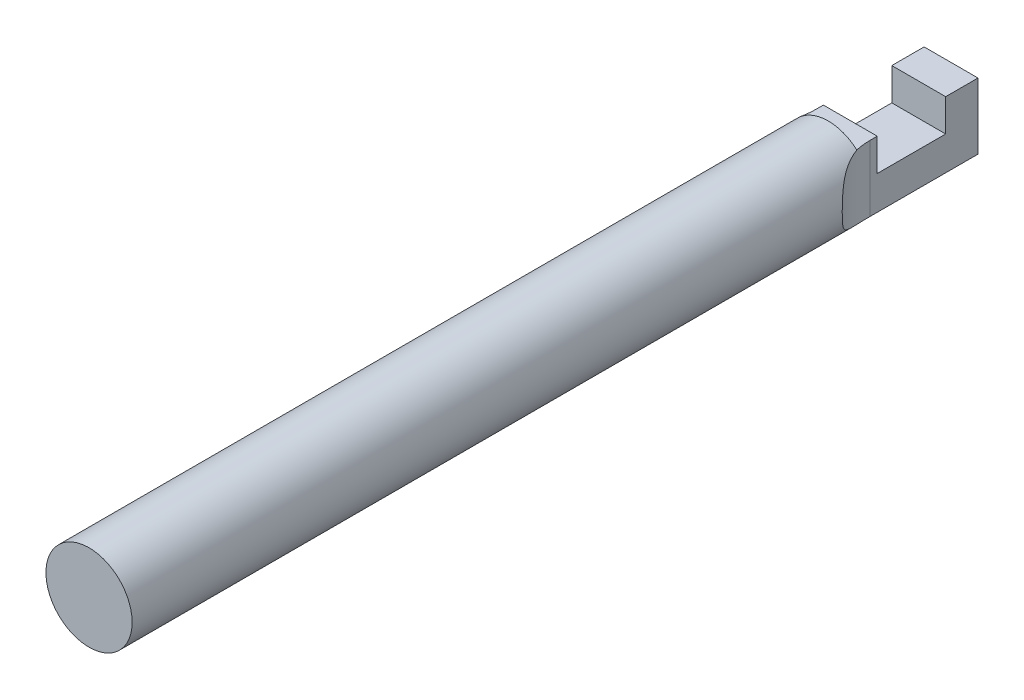
SolidWorks part; units mm, degrees
material "Alloy Steel"
ref_plane "Front" through (0, 0, 0) normal (0, 0, 1) x (1, 0, 0)
ref_plane "Top" through (0, 0, 0) normal (0, 1, 0) x (1, 0, 0)
ref_plane "Right" through (0, 0, 0) normal (1, 0, 0) x (0, 0, -1)
ref_axis "X" through (-80.9, 0, 0) along (1, 0, 0)
ref_axis "Y" through (0, -50, 0) along (0, 1, 0)
ref_axis "Z" through (0, 0, -80.9) along (0, 0, 1)
sketch "Sketch1" plane through (0, 0, 0) normal (1, 0, 0) x (0, 0, -1)
  line L0 (0, 0) -> (0, 2)
  line L1 (-40, 2) -> (-40, 0)
  line L2 (-40, 0) -> (0, 0)
  line L3 (-40, 2) -> (0, 2)
  line L4 (0.7212, 0) -> (9.8841, 0) construction
  dimension "D1" = 4
  dimension "D2" = 40
revolve "Revolve1" add sketch "Sketch1" angle 360 about L4
sketch "Sketch2" plane through (0, 0, 0) normal (0, 1, 0) x (1, 0, 0)
  line L0 (-1.25, 0) -> (-1.25, -5)
  line L1 (2, 0) -> (-2, 0) construction
  line L2 (1.25, 0) -> (1.25, -5)
  line L3 (4.425, -8.175) -> (4.425, 0)
  line L4 (4.425, 0) -> (1.25, 0)
  line L5 (-1.25, 0) -> (-4.425, 0)
  line L6 (-4.425, 0) -> (-4.425, -8.175)
  line L7 (0, 8.3405) -> (0, 0) construction
  arc A0 (-1.25, -5) -> (-4.425, -8.175) centre (-4.425, -5) cw
  arc A1 (1.25, -5) -> (4.425, -8.175) centre (4.425, -5) ccw
  dimension "D1" = 3.175
  dimension "D2" = 2.5
  dimension "D3" = 5
extrude "Cut-Extrude1" cut sketch "Sketch2" along normal through all both and the other way through all
sketch "Sketch3" plane through (0, 0, 0) normal (0, 1, 0) x (1, 0, 0)
  line L0 (-2, 0) -> (-2, -5.7)
  line L1 (-2, -5.7) -> (2, -5.7)
  line L2 (2, -5.7) -> (2, 0)
  line L3 (2, 0) -> (-2, 0)
  point P6 (1.7321, -5.8304)
  point P9 (-2.1022, -7.7072)
  point P11 (0, 0)
  dimension "D1" = 4
  dimension "D2" = 5.7
extrude "Cut-Extrude2" cut sketch "Sketch3" along normal through all from offset 1.5
sketch "Sketch4" plane through (0, 0, 0) normal (0, 1, 0) x (1, 0, 0)
  line L0 (-1.25, -1.5) -> (1.25, -1.5)
  line L1 (-1.25, 0) -> (-1.25, -5) construction
  line L2 (1.25, -5) -> (1.25, 0) construction
  line L3 (1.25, -1.5) -> (1.25, -4.675)
  line L4 (1.25, -4.675) -> (-1.25, -4.675)
  line L6 (-1.25, -4.675) -> (-1.25, -1.5)
  line L7 (1.25, 0) -> (-1.25, 0) construction
  dimension "D1" = 1.5
  dimension "D2" = 3.175
extrude "Cut-Extrude3" cut sketch "Sketch4" along normal through all
